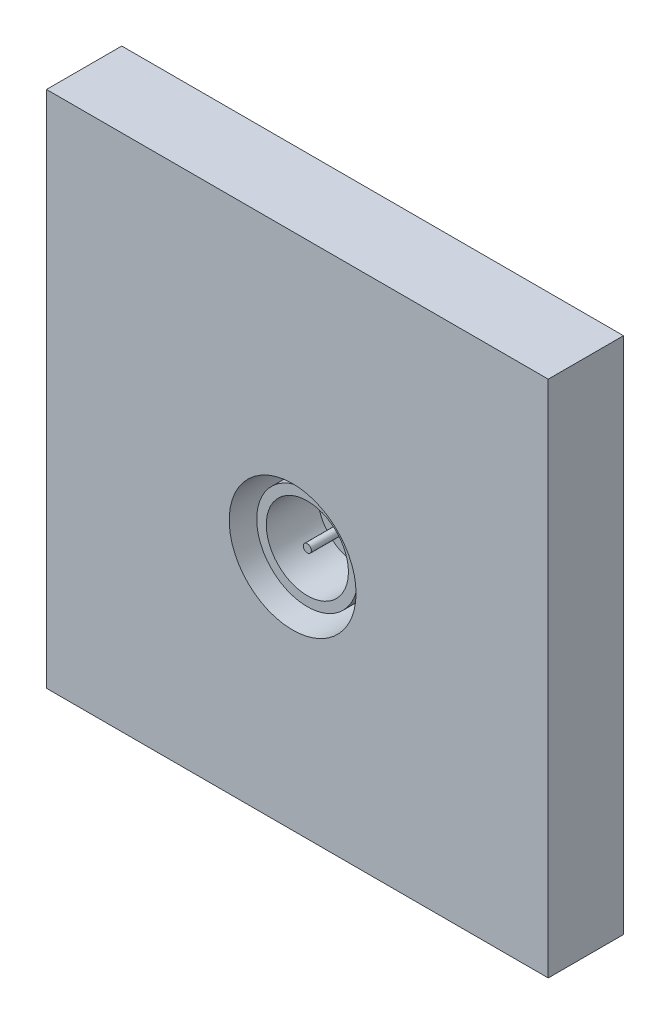
SolidWorks part; units mm, degrees
ref_plane "Front Plane" through (0, 0, 0) normal (0, 0, 1) x (1, 0, 0)
ref_plane "Top Plane" through (0, 0, 0) normal (0, 1, 0) x (1, 0, 0)
ref_plane "Right Plane" through (0, 0, 0) normal (1, 0, 0) x (0, 0, -1)
sketch "Sketch1" plane through (0, 0, 0) normal (1, 0, 0) x (0, 0, -1)
  line L1 (-943.5108, -6167.6517) -> (635.1912, -6167.6517)
  line L2 (-943.5108, -6167.6517) -> (-943.5108, 4711.3099)
  line L3 (-943.5108, 4711.3099) -> (635.1912, 4711.3099)
  line L4 (635.1912, -6167.6517) -> (635.1912, 4711.3099)
extrude "Boss-Extrude1" add sketch "Sketch1" along normal blind 6196 and the other way blind 4329
sketch "Sketch3" plane through (0, 0, 943.5108) normal (0, 0, 1) x (1, 0, 0)
  circle A0 centre (833.9306, -1197.1664) radius 1330.4493
extrude "Cut-Extrude1" cut sketch "Sketch3" against normal blind 1384
sketch "Sketch4" plane through (0, 0, -635.1912) normal (0, 0, -1) x (-1, 0, 0)
  circle A0 centre (-833.9306, -1197.1664) radius 84.8072
extrude "Boss-Extrude2" add sketch "Sketch4" against normal blind 1270
sketch "Sketch5" plane through (0, 0, -635.1912) normal (0, 0, -1) x (-1, 0, 0)
  circle A0 centre (-833.9306, -1197.1664) radius 1061.6158
  circle A1 centre (-833.9306, -1197.1664) radius 861.2734
extrude "Boss-Extrude3" add sketch "Sketch5" along normal blind 10
extrude "Boss-Extrude4" add sketch "Sketch5<2>" against normal blind 1270 contours A0 A1 region at (1865.5194, -1197.1664, -635.1912)
sketch "Sketch5<2>" plane through (0, 0, -635.1912) normal (0, 0, -1) x (-1, 0, 0) same geometry as "Sketch5"
